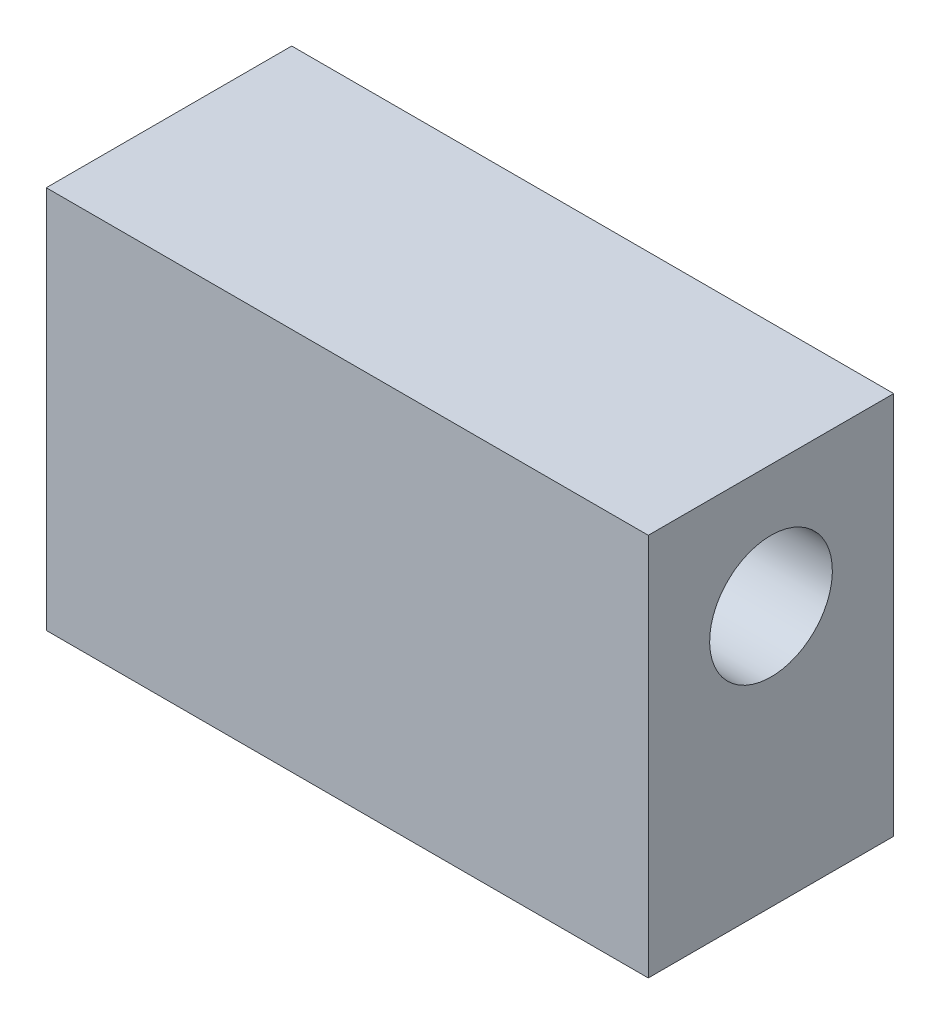
SolidWorks part; units mm, degrees
material "1060 Alloy"
ref_plane "Front" through (0, 0, 0) normal (0, 0, 1) x (1, 0, 0)
ref_plane "Top" through (0, 0, 0) normal (0, 1, 0) x (1, 0, 0)
ref_plane "Right" through (0, 0, 0) normal (1, 0, 0) x (0, 0, -1)
sketch "Sketch3" plane through (0, 0, 0) normal (0, 0, 1) x (1, 0, 0)
  line L0 (-0.127, -6.35) -> (30.1755, -6.35)
  line L1 (0, 0) -> (31.1484, 0)
  line L2 (0, 0) -> (0, -19.8376)
  line L3 (0, -19.8376) -> (31.1484, -19.8376)
  line L4 (31.1484, 0) -> (31.1484, -19.8376)
  line L5 (15.5742, -19.8376) -> (15.5742, 0) construction
  line L6 (15.5742, -6.35) -> (8.0621, -19.3614) construction
  line L15 (12.5496, -11.5887) -> (15.5742, -13.335) construction
  line L16 (15.5742, -6.35) -> (22.9274, -19.0862) construction
  circle A0 centre (15.5742, -6.35) radius 6.0492 construction
  point P14 (0, -6.35)
  point P17 (9.525, -6.35)
  point P19 (31.1484, -6.35)
  point P20 (7.7871, -19.8376)
  point P24 (23.3613, -19.8376)
  dimension "D2" = 6.35
  dimension "D6" = 3.4925
  dimension "D3" = 60
  dimension "D1" = 9.525
  dimension "D4" = 9.525
  dimension "D5" = 60
extrude "Boss-Extrude1" add sketch "Sketch3" along normal mid plane 12.7
sketch "Sketch4" plane through (0, 0, 0) normal (-1, 0, 0) x (0, 0, 1)
  circle A0 centre (0, -6.35) radius 3.175
  dimension "D1" = 6.35
extrude "Cut-Extrude1" cut sketch "Sketch4" against normal blind 9.525
ref_plane "Plane1" through (7.7871, -19.8376, 0) normal (-0.5, -0.866, 0) x (-0.866, 0.5, 0)
ref_plane "Mirror Plane" through (15.5742, 0, 0) normal (-1, 0, 0) x (0, 0, 1)
sketch "Sketch5" plane through (7.7871, -19.8376, 0) normal (-0.5, -0.866, 0) x (-0.866, 0.5, 0)
  circle A0 centre (0, 0) radius 3.175
  dimension "D1" = 6.35
extrude "Cut-Extrude5" cut sketch "Sketch5" against normal blind 9.525 and the other way up to next
sketch "Sketch6" plane through (0, 0, -6.35) normal (0, 0, -1) x (-1, 0, 0)
  circle A0 centre (-15.5742, -6.35) radius 3.175
  dimension "D1" = 6.35
extrude "Cut-Extrude6" cut sketch "Sketch6" against normal blind 9.525
mirror "Mirror1" about plane through (15.5742, 0, 0) normal (-1, 0, 0) of "Cut-Extrude1", "Cut-Extrude5"
equation "\"truss_member_od\"= .25in"
equation "\"truss_member_id\"= 0in"
equation "\"truss_member_L1\"= 2.125in"
equation "\"connector_hole_depth\"= .375in"
equation "\"D1@Boss-Extrude1\"=\"truss_member_od\"*2"
equation "\"D6@Sketch3\"=\"truss_member_od\"/2*1.1"
equation "\"D1@Sketch4\"=\"truss_member_od\""
equation "\"D1@Cut-Extrude1\"=\"connector_hole_depth\""
equation "\"D1@Sketch3\"=\"connector_hole_depth\""
equation "\"D4@Sketch3\"=\"connector_hole_depth\""
equation "\"D1@Sketch5\"=\"truss_member_od\""
equation "\"D1@Cut-Extrude5\"=\"connector_hole_depth\""
equation "\"D1@Cut-Extrude6\"=\"connector_hole_depth\""
equation "\"D1@Sketch6\"=\"truss_member_od\""
